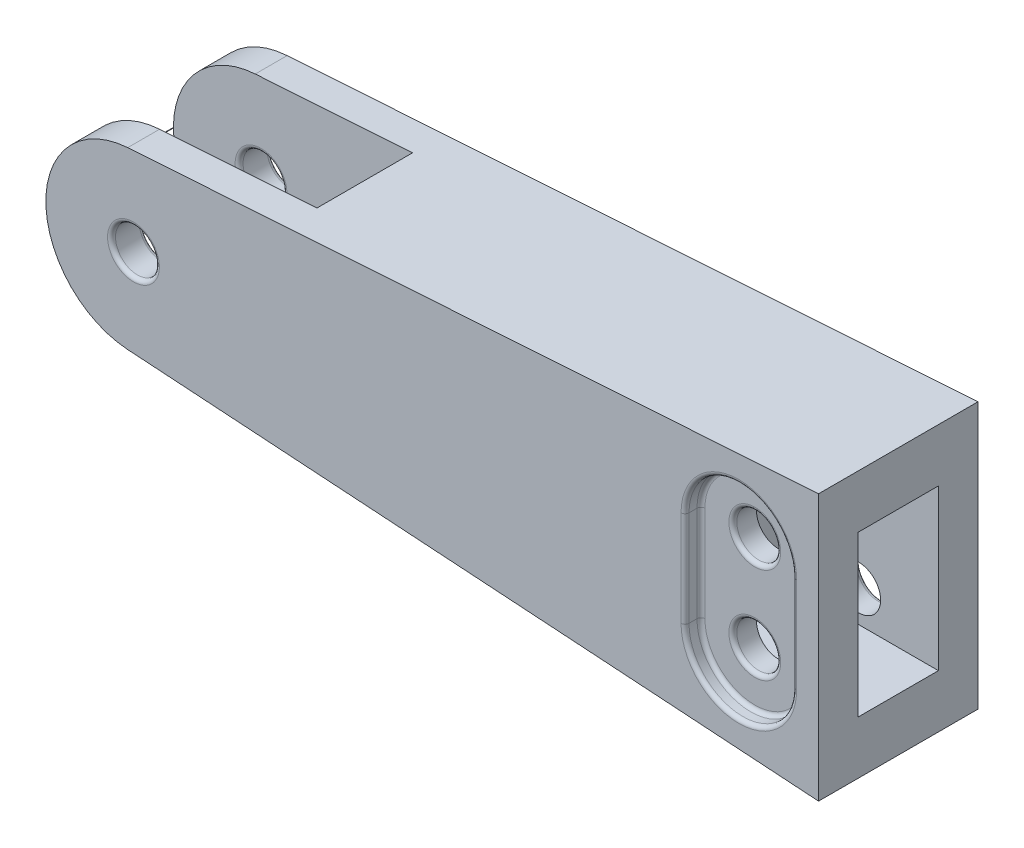
SolidWorks part; units mm, degrees
ref_plane "Front Plane" through (0, 0, 0) normal (0, 0, 1) x (1, 0, 0)
ref_plane "Top Plane" through (0, 0, 0) normal (0, 1, 0) x (1, 0, 0)
ref_plane "Right Plane" through (0, 0, 0) normal (1, 0, 0) x (0, 0, -1)
sketch "Sketch1" plane through (0, 0, 0) normal (0, 0, 1) x (1, 0, 0)
  line L1 (43.0973, 0) -> (50043.0973, 0) construction
  line L2 (0, 21.9801) -> (0, 50021.9801) construction
  line L5 (-147.5823, 10.9687) -> (-60.9236, 16.6957)
  line L6 (-60.9236, -16.6957) -> (-17.5178, -19.5642) construction
  line L7 (-60.9236, 16.6957) -> (-60.9236, -16.6957) construction
  line L8 (-60.9236, 16.6957) -> (-60.9236, -16.6957)
  line L9 (-147.5823, -10.9687) -> (-60.9236, -16.6957)
  arc A1 (-147.5823, 10.9687) -> (-147.5823, -10.9687) centre (-146.8574, 0) ccw
  point P9 (0, 0)
  dimension "D1" = 146.8574
extrude "Boss-Extrude1" add sketch "Sketch1" along normal up to surface (20 mm away) contours A1 region at (-104.6886, 0, 0)
sketch "Sketch2" plane through (-60.9236, 0, 0) normal (1, 0, 0) x (0, 0, -1)
  line L0 (-10, -20) -> (-10, 20) construction
  line L4 (-15.035, -10.035) -> (-4.965, -10.035)
  line L5 (-15.035, -10.035) -> (-15.035, 10.035)
  line L6 (-15.035, 10.035) -> (-4.965, 10.035)
  line L16 (-20, -20) -> (0, -20) construction
  line L17 (-20, 20) -> (-20, -20) construction
  line L18 (0, 20) -> (-20, 20) construction
  line L19 (0, -20) -> (0, 20) construction
  line L20 (-4.965, -10.035) -> (-4.965, 10.035)
  line L21 (-15.035, -10.035) -> (-4.965, 10.035) construction
  line L22 (-15.035, 10.035) -> (-4.965, -10.035) construction
  line L23 (0, 0) -> (-20, 0) construction
  point P2 (-10, 0)
  point P15 (-10, 0)
  dimension "D2" = 10.07
  dimension "D3" = 20.07
  dimension "D1" = 40
  dimension "D4" = 20
  dimension "D5" = 10
extrude "Cut-Extrude1" cut sketch "Sketch2" against normal blind 20
sketch "Sketch4" plane through (0, 0, 0) normal (0, 1, 0) x (1, 0, 0)
  line L0 (-60.9236, -20) -> (-147.5823, -20) construction
  line L5 (-157.85, 0) -> (-157.85, -20) construction
  line L6 (-157.85, -4) -> (-127.85, -4)
  line L7 (-157.85, -4) -> (-157.85, -16)
  line L10 (-157.85, -16) -> (-127.85, -16)
  line L15 (-127.85, -4) -> (-127.85, -16)
  line L16 (-157.85, -4) -> (-127.85, -16) construction
  line L17 (-157.85, -16) -> (-127.85, -4) construction
  line L18 (-147.5823, 0) -> (-157.8501, 0) construction
  point P4 (-142.85, -10)
  dimension "D1" = 4
  dimension "D2" = 4
  dimension "D3" = 30
extrude "Cut-Extrude2" cut sketch "Sketch4" against normal through all both and the other way through all
sketch "Sketch5" plane through (0, 0, 0) normal (0, 0, -1) x (-1, 0, 0)
  circle A0 centre (146.8574, 0) radius 2.75
  dimension "D1" = 5.5
extrude "Cut-Extrude3" cut sketch "Sketch5" against normal through all
sketch "Sketch6" plane through (0, 0, 0) normal (0, 0, -1) x (-1, 0, 0)
  line L1 (0, 0) -> (50000, 0) construction
  line L2 (60.9236, 16.6957) -> (60.9236, -16.6957) construction
  circle A0 centre (70.9236, -6) radius 2.75
  circle A1 centre (70.9236, 6) radius 2.75
  dimension "D1" = 5.5
  dimension "D2" = 10
  dimension "D3" = 6
extrude "Cut-Extrude4" cut sketch "Sketch6" against normal through all
sketch "Sketch8" plane through (0, 0, 0) normal (0, 0, -1) x (-1, 0, 0)
  line L0 (64.1736, 6) -> (64.1736, -6)
  line L2 (77.6736, 6) -> (77.6736, -6)
  circle A0 centre (70.9236, -6) radius 2.75 construction
  circle A1 centre (70.9236, 6) radius 2.75 construction
  circle A2 centre (70.9236, -6) radius 2.75 construction
  circle A3 centre (70.9236, 6) radius 2.75 construction
  arc A4 (64.1736, -6) -> (77.6736, -6) centre (70.9236, -6) ccw
  arc A5 (77.6736, 6) -> (64.1736, 6) centre (70.9236, 6) ccw
  circle A6 centre (70.9236, 6) radius 6.75 construction
  circle A7 centre (70.9236, -6) radius 6.75 construction
  dimension "D1" = 4
extrude "Cut-Extrude5" cut sketch "Sketch8" against normal blind 2
ref_plane "Plane1" through (0, 0, 10) normal (0, 0, -1) x (-1, 0, 0)
mirror "Mirror1" about plane through (0, 0, 10) normal (0, 0, -1) of "Cut-Extrude5"
fillet "Fillet2" radius 0.5 24 edges at (-70.9236, -12.75, 2) (-64.1736, 0, 2) (-70.9236, 12.75, 2) (-70.9236, -12.75, 0) (-64.1736, 0, 0) (-70.9236, 12.75, 0) (-70.9236, -12.75, 18) (-64.1736, 0, 18) (-70.9236, 12.75, 18) (-70.9236, -12.75, 20) (-64.1736, 0, 20) (-70.9236, 12.75, 20) (-149.6074, 0, 4) (-149.6074, 0, 0) (-144.1074, 0, 16) (-149.6074, 0, 20) (-68.1736, -6, 18) (-68.1736, 6, 18) (-73.6736, -6, 2) (-73.6736, 6, 2) (-77.6736, 0, 18) (-77.6736, 0, 20) (-77.6736, 0, 2) (-77.6736, 0, 0)
